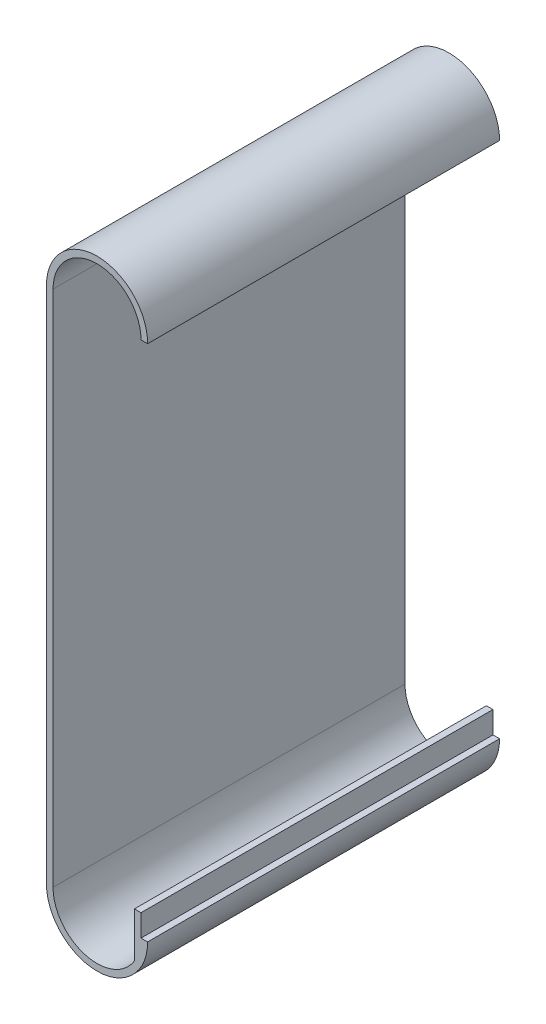
SolidWorks part; units mm, degrees
ref_plane "Front Plane" through (0, 0, 0) normal (0, 0, 1) x (1, 0, 0)
ref_plane "Top Plane" through (0, 0, 0) normal (0, 1, 0) x (1, 0, 0)
ref_plane "Right Plane" through (0, 0, 0) normal (1, 0, 0) x (0, 0, -1)
sketch "Sketch1" plane through (0, 0, 0) normal (0, 0, 1) x (1, 0, 0)
  line L0 (0, -75) -> (-40, -75) construction
  line L1 (33, 42.75) -> (-40, 42.75) construction
  line L3 (-40, -75) -> (-40, 160.5)
  line L4 (-43, -75) -> (-43, 160.5)
  line L5 (0, 160.5) -> (3, 160.5)
  line L6 (0, -75) -> (3, -75)
  arc A0 (-40, -75) -> (0, -75) centre (-20, -75) ccw
  arc A1 (-40, 160.5) -> (0, 160.5) centre (-20, 160.5) cw
  arc A2 (-43, 160.5) -> (3, 160.5) centre (-20, 160.5) cw
  arc A3 (-43, -75) -> (3, -75) centre (-20, -75) ccw
  dimension "D1" = 3
extrude "Boss-Extrude1" add sketch "Sketch1" against normal up to surface (160 mm away)
ref_plane "Plane1" through (3, 0, 0) normal (1, 0, 0) x (0, 0, -1)
sketch "Sketch5" plane through (0, 0, -160) normal (0, 0, -1) x (-1, 0, 0)
  line L1 (3, -65) -> (0, -65)
  line L2 (3, -65) -> (3, -86.3578)
  line L3 (3, -86.3578) -> (0, -86.3578)
  line L4 (0, -65) -> (0, -86.3578)
  arc A0 (-3, -75) -> (43, -75) centre (20, -75) ccw construction
  dimension "D1" = 3
extrude "Boss-Extrude4" add sketch "Sketch5" against normal up to surface (160 mm away) up to face at (-20, 42.75, 0)
